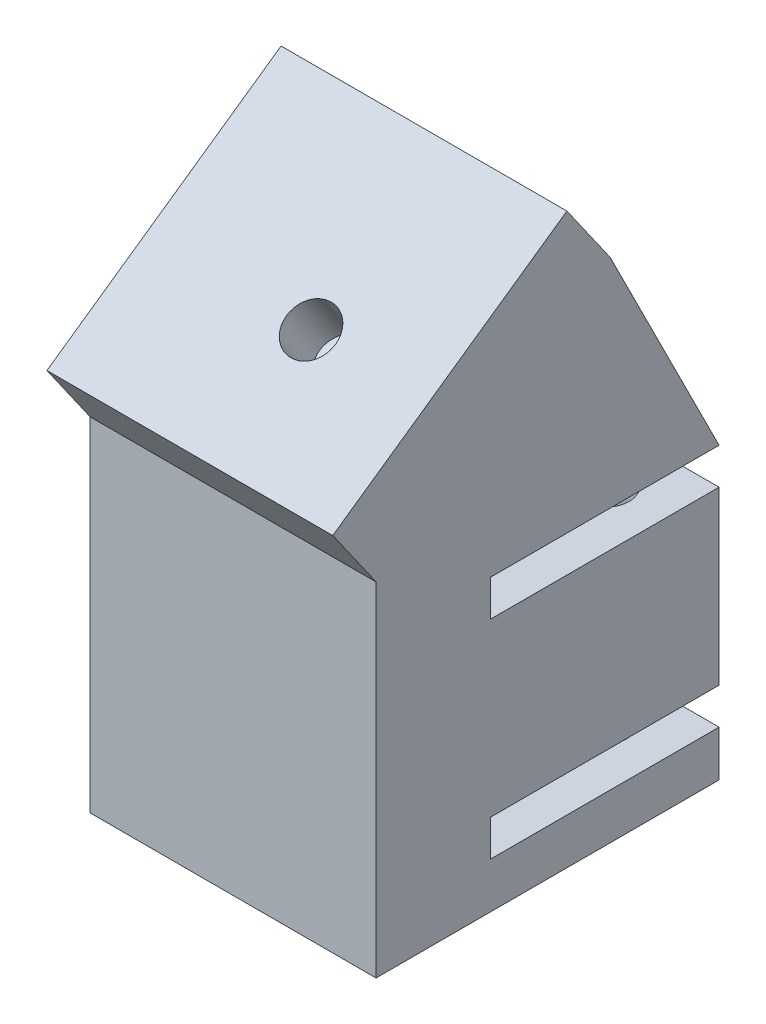
SolidWorks part; units mm, degrees
ref_plane "Front Plane" through (0, 0, 0) normal (0, 0, 1) x (1, 0, 0)
ref_plane "Top Plane" through (0, 0, 0) normal (0, 1, 0) x (1, 0, 0)
ref_plane "Right Plane" through (0, 0, 0) normal (1, 0, 0) x (0, 0, -1)
sketch "Sketch1" plane through (0, 0, 0) normal (1, 0, 0) x (0, 0, -1)
  line L0 (20, 0) -> (0, 0)
  line L1 (20, 0) -> (20, -15)
  line L2 (20, -15) -> (0, -15)
  line L3 (0, -15) -> (0, -18.175)
  line L4 (0, -18.175) -> (20, -18.175)
  line L5 (20, -18.175) -> (20, -22.175)
  line L6 (20, -22.175) -> (-10, -22.175)
  line L7 (-10, -22.175) -> (-10, 7.825)
  line L8 (-10, 7.825) -> (10.4788, 22.1644)
  line L10 (0, 0) -> (0, 3.175)
  line L11 (0, 3.175) -> (20, 3.175)
  line L12 (20, 3.175) -> (10.4788, 22.1644)
  dimension "D1" = 3.175
  dimension "D2" = 15
  dimension "D3" = 4
  dimension "D4" = 20
  dimension "D5" = 30
  dimension "D6" = 25
  dimension "D7" = 125
  dimension "D8" = 30
extrude "Boss-Extrude1" add sketch "Sketch1" along normal blind 25
sketch "Sketch2" plane through (0, 9.9491, 6.9664) normal (0, 0.8192, 0.5736) x (1, 0, 0)
  line L1 (0, 21.2967) -> (21, 21.2967)
  line L2 (0, 21.2967) -> (0, 0.2967)
  line L3 (0, 0.2967) -> (21, 0.2967)
  line L4 (21, 21.2967) -> (21, 0.2967)
  line L5 (0, 21.2967) -> (25, 21.2967)
  line L6 (0, 21.2967) -> (0, -3.7033)
  line L7 (0, -3.7033) -> (25, -3.7033)
  line L8 (25, 21.2967) -> (25, -3.7033)
  line M5 (0, 21.2967) -> (0, -3.7033)
  line M6 (0, -3.7033) -> (25, -3.7033)
  line M7 (25, -3.7033) -> (25, 21.2967)
  line M8 (25, 21.2967) -> (0, 21.2967)
  dimension "D1" = 4
  dimension "D2" = 4
extrude "Boss-Extrude2" add sketch "Sketch2" along normal blind 1.6 contours L4 L3 M8 M5 M6 M7 region at (23, 21.9616, -10.1892)
sketch "Sketch3" plane through (0, 11.2598, 7.8842) normal (0, 0.8192, 0.5736) x (1, 0, 0)
  line L1 (25, -3.7033) -> (0, -3.7033)
  line L2 (25, -3.7033) -> (25, 21.2967)
  line L3 (25, 21.2967) -> (0, 21.2967)
  line L4 (0, -3.7033) -> (0, 21.2967)
extrude "Boss-Extrude3" add sketch "Sketch3" along normal blind 5
sketch "Sketch4" plane through (0, 15.3555, 10.7521) normal (0, 0.8192, 0.5736) x (1, 0, 0)
  line L0 (25, -3.7033) -> (25, 21.2967) construction
  line L1 (0, -3.7033) -> (25, -3.7033) construction
  circle A0 centre (14.5, 6.7967) radius 2.15
  dimension "D1" = 4.3
  dimension "D2" = 10.5
  dimension "D3" = 10.5
extrude "Cut-Extrude1" cut sketch "Sketch4" against normal up to surface (5 mm away) up to face at (10.5, 17.4525, -0.96)
sketch "Sketch5" plane through (0, 15.3555, 10.7521) normal (0, 0.8192, 0.5736) x (1, 0, 0)
  circle A0 centre (14.5, 6.7967) radius 1.85
  dimension "D1" = 3.7
extrude "Cut-Extrude2" cut sketch "Sketch5" against normal blind 13
sketch "Sketch6" plane through (0, -18.175, 0) normal (0, 1, 0) x (1, 0, 0)
  line L0 (0, 20) -> (0, 10.4788) construction
  line L1 (25, 20) -> (0, 20) construction
  line L2 (25, 20) -> (25, 10.4788) construction
  circle A0 centre (5, 15) radius 1.85
  circle A1 centre (20, 15) radius 1.85
  dimension "D1" = 3.7
  dimension "D2" = 3.7
  dimension "D3" = 5
  dimension "D4" = 5
  dimension "D5" = 5
  dimension "D6" = 5
extrude "Cut-Extrude3" cut sketch "Sketch6" against normal blind 13
sketch "Sketch7" plane through (0, -15, 0) normal (0, -1, 0) x (1, 0, 0)
  circle A0 centre (5, -15) radius 2.15
  circle A1 centre (20, -15) radius 2.15
  dimension "D1" = 4.3
extrude "Cut-Extrude4" cut sketch "Sketch7" against normal blind 43
sketch "Sketch8" plane through (0, 0, 0) normal (0, 1, 0) x (1, 0, 0)
  circle A0 centre (5, 15) radius 4
  circle A1 centre (20, 15) radius 4
  dimension "D1" = 8
extrude "Cut-Extrude5" cut sketch "Sketch8" along normal blind 67 from offset 7
equation "\"D2@Sketch6\"=\"D1@Sketch6\""
equation "\"D2@Sketch4\"=\"D3@Sketch4\""
